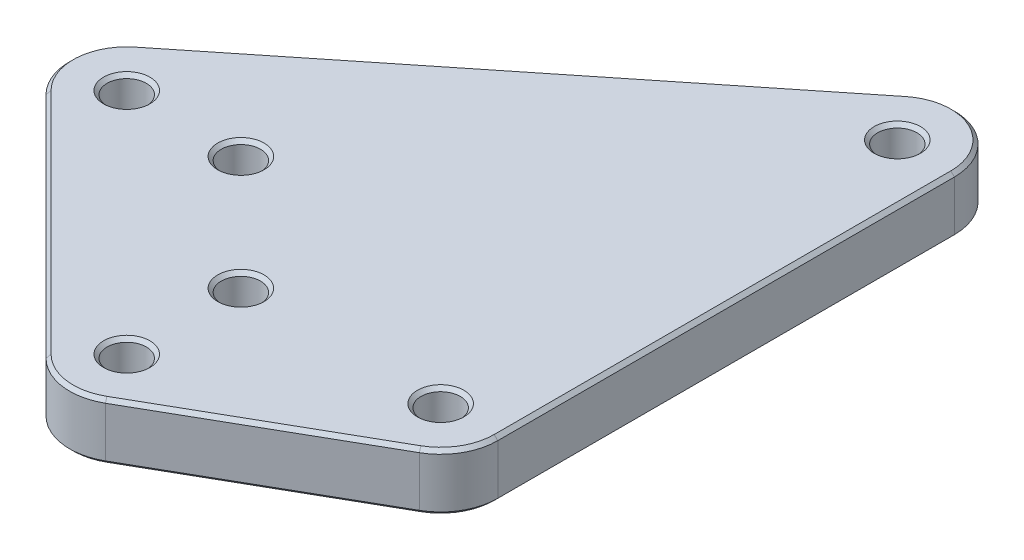
SolidWorks part; units mm, degrees
ref_plane "Front Plane" through (0, 0, 0) normal (0, 0, 1) x (1, 0, 0)
ref_plane "Top Plane" through (0, 0, 0) normal (0, 1, 0) x (1, 0, 0)
ref_plane "Right Plane" through (0, 0, 0) normal (1, 0, 0) x (0, 0, -1)
sketch "Sketch1" plane through (0, 0, 0) normal (0, 1, 0) x (1, 0, 0)
  line L14 (-51.5918, 17.6585) -> (-3.9668, 55.7585)
  line L15 (6.35, 50.8) -> (6.35, 0)
  line L16 (3.1505, -5.5133) -> (-19.0745, -18.2133)
  line L17 (-52.1151, 8.2099) -> (-26.7151, -17.1901)
  circle A0 centre (0, 0) radius 2.1828
  circle A1 centre (0, 50.8) radius 2.1828
  circle A2 centre (-22.225, 0) radius 2.1828
  circle A3 centre (-22.225, -12.7) radius 2.1828
  circle A4 centre (-34.925, 12.7) radius 2.1828
  circle A5 centre (-47.625, 12.7) radius 2.1828
  arc A13 (-51.5918, 17.6585) -> (-52.1151, 8.2099) centre (-47.625, 12.7) ccw
  arc A14 (6.35, 50.8) -> (-3.9668, 55.7585) centre (0, 50.8) ccw
  arc A15 (3.1505, -5.5133) -> (6.35, 0) centre (0, 0) ccw
  arc A16 (-26.7151, -17.1901) -> (-19.0745, -18.2133) centre (-22.225, -12.7) ccw
  dimension "D1" = 4.3656
  dimension "D2" = 4.3656
  dimension "D4" = 4.3656
  dimension "D7" = 4.3656
  dimension "D10" = 4.3656
  dimension "D12" = 4.3656
  dimension "D13" = 12.7
  dimension "D14" = 12.7
  dimension "D15" = 12.7
  dimension "D16" = 12.7
  dimension "D3" = 50.8
  dimension "D5" = 22.225
  dimension "D6" = 12.7
  dimension "D8" = 12.7
  dimension "D9" = 12.7
  dimension "D11" = 12.7
extrude "Boss-Extrude1" add sketch "Sketch1" along normal blind 6.35
chamfer "Chamfer1" distance 0.3969 angle 45 28 edges at (-47.625, 0, -10.5172) (-34.925, 0, -10.5172) (-22.225, 0, 14.8828) (-22.225, 0, 2.1828) (0, 0, -48.6172) (0, 0, 2.1828) (-39.4151, 0, 4.4901) (-23.0679, 0, 18.9938) (-7.962, 0, 11.8633) (5.4922, 0, 3.1872) (6.35, 0, -25.4) (2.7507, 0, -56.5233) (-27.7793, 0, -36.7085) (-53.9653, 0, -13.0512) (-47.625, 6.35, -10.5172) (-22.225, 6.35, 14.8828) (0, 6.35, -48.6172) (-27.7793, 6.35, -36.7085) (2.7507, 6.35, -56.5233) (6.35, 6.35, -25.4) (5.4922, 6.35, 3.1872) (-7.962, 6.35, 11.8633) (-23.0679, 6.35, 18.9938) (-39.4151, 6.35, 4.4901) (-53.9653, 6.35, -13.0512) (0, 6.35, 2.1828) (-22.225, 6.35, 2.1828) (-34.925, 6.35, -10.5172)
